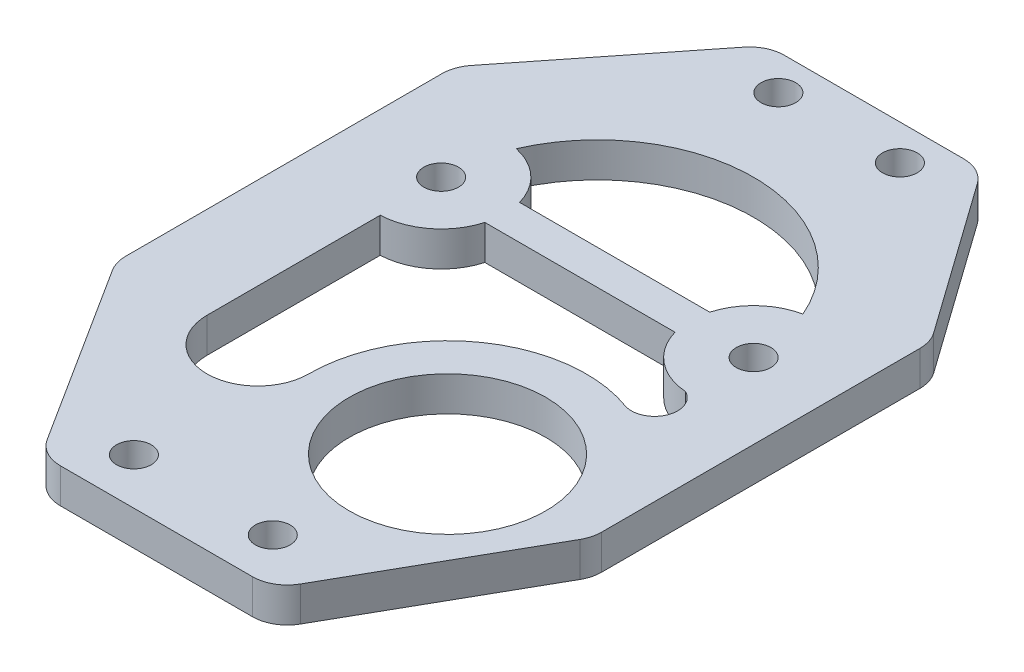
SolidWorks part; units mm, degrees
note: The reader was unsure of these and kept them because the rebuilt part matched: thickness of "Base-Flange1", "Sheet-Metal1".
ref_plane "Front Plane" through (0, 0, 0) normal (0, 0, 1) x (1, 0, 0)
ref_plane "Top Plane" through (0, 0, 0) normal (0, 1, 0) x (1, 0, 0)
ref_plane "Right Plane" through (0, 0, 0) normal (1, 0, 0) x (0, 0, -1)
sketch "Sketch1" plane through (0, 0, 0) normal (0, 1, 0) x (1, 0, 0)
  line L0 (0, 34.5262) -> (0, -34.5262) construction
  line L1 (-42.1133, 0) -> (42.1133, 0) construction
  line L2 (19.6094, -14.0594) -> (10.8621, -29.4802)
  line L3 (-7.7982, 31) -> (7.7021, 31)
  line L5 (-8.3526, -31) -> (8.2527, -31)
  line L6 (20, 14.9247) -> (20, -12.5792)
  line L7 (13.5, 7.05) -> (-13.5, 7.05) construction
  line L8 (10.147, 29.7386) -> (19.4449, 16.6633)
  line L9 (-13.2814, 0) -> (-13.2814, 1.568)
  line L10 (-8.2227, 8.55) -> (8.2085, 8.55)
  line L11 (-20.564, 16.7008) -> (-10.1508, 29.8615)
  line L12 (-21.2114, 14.8393) -> (-21.2114, -12.4977)
  line L13 (-13.2814, -13.4) -> (-13.2814, 0)
  line L14 (-20.7429, -14.1076) -> (-10.884, -29.6099)
  line L15 (-8.2227, 5.55) -> (8.2085, 5.55)
  circle A0 centre (7.5, -13.4) radius 8.5
  circle A1 centre (6, -27) radius 1.5
  circle A2 centre (-6, -27) radius 1.5
  arc A3 (11.6553, -2.1424) -> (13.1131, 1.5636) centre (12.21, -0.2209) ccw
  arc A4 (11.6553, -2.1424) -> (-4.5, -13.4) centre (7.5, -13.4) ccw
  arc A5 (-13.2814, -13.4) -> (-4.5, -13.4) centre (-8.8907, -13.4) ccw
  circle A6 centre (5.25, 27.9408) radius 1.5
  circle A7 centre (-5.25, 27.9408) radius 1.5
  circle A8 centre (13.5, 7.05) radius 1.5
  arc A9 (12.3796, 12.4347) -> (8.2085, 8.55) centre (13.5, 7.05) ccw
  arc A11 (12.3796, 12.4347) -> (-12.3852, 12.4219) centre (0, 7.05) ccw
  circle A12 centre (-13.5, 7.05) radius 1.5
  arc A13 (-13.2814, 1.568) -> (-8.2227, 5.55) centre (-13.5, 7.05) ccw
  arc A14 (-10.1508, 29.8615) -> (-7.7982, 31) centre (-7.7982, 28) cw
  arc A15 (-21.2114, -12.4977) -> (-20.7429, -14.1076) centre (-18.2114, -12.4977) ccw
  arc A16 (-21.2114, 14.8393) -> (-20.564, 16.7008) centre (-18.2114, 14.8393) cw
  arc A17 (-10.884, -29.6099) -> (-8.3526, -31) centre (-8.3526, -28) ccw
  arc A18 (10.8621, -29.4802) -> (8.2527, -31) centre (8.2527, -28) cw
  arc A19 (19.6094, -14.0594) -> (20, -12.5792) centre (17, -12.5792) ccw
  arc A20 (19.4449, 16.6633) -> (20, 14.9247) centre (17, 14.9247) cw
  arc A21 (10.147, 29.7386) -> (7.7021, 31) centre (7.7021, 28) ccw
  arc A22 (-8.2227, 8.55) -> (-12.3852, 12.4219) centre (-13.5, 7.05) ccw
  arc A23 (8.2085, 5.55) -> (13.1131, 1.5636) centre (13.5, 7.05) ccw
  point P0 (0, 0)
  point P4 (0, 0)
  point P8 (0, 0)
  point P36 (-9.25, 31)
  point P50 (-10, -31)
  point P53 (10, -31)
  point P56 (20, -13.3709)
  point P61 (9.25, 31)
  dimension "D2" = 17.6
  dimension "D4" = 17
  dimension "D5" = 4
  dimension "D9" = 62
  dimension "D10" = 20.45
  dimension "D12" = 13.15
  dimension "D14" = 4
  dimension "D15" = 12
  dimension "D16" = 10.5
  dimension "D18" = 3
  dimension "D19" = 13.5
  dimension "D20" = 11
  dimension "D22" = 4
  dimension "D24" = 3
  dimension "D25" = 3
  dimension "D3" = 7.5
  dimension "D6" = 4
  dimension "D7" = 6
  dimension "D8" = 12
  dimension "D11" = 4
  dimension "D13" = 4.71
  dimension "D17" = 5.25
  dimension "D21" = 7.93
  dimension "D23" = 6.5
base flange "Base-Flange1" sketch "Sketch1" thickness 3 reverse thickness direction yes parameters "D1"=0.7366
sketch "Bend-Lines1" [suppressed] plane through (0, 0, 0) normal (0, 1, 0) x (1, 0, 0)
sketch "Bounding-Box1" [suppressed] plane through (0, 0, 0) normal (0, 1, 0) x (1, 0, 0)
sheet metal parameters "Sheet-Metal1" thickness 3 parameters "D1"=0.7366
flat pattern "Flat-Pattern1" [suppressed]
sketch "Bend-Lines2" plane through (0, 0, 0) normal (0, 1, 0) x (1, 0, 0)
sketch3d "Bounding-Box2" [suppressed]
  line L0 (13.4132, -59, 0) -> (13.4132, 3, 0) construction
  line L1 (-27.7982, -59, 0) -> (-27.7982, 3, 0) construction
  line L2 (13.4132, -59, 0) -> (-27.7982, -59, 0) construction
  line L3 (13.4132, 3, 0) -> (-27.7982, 3, 0) construction
